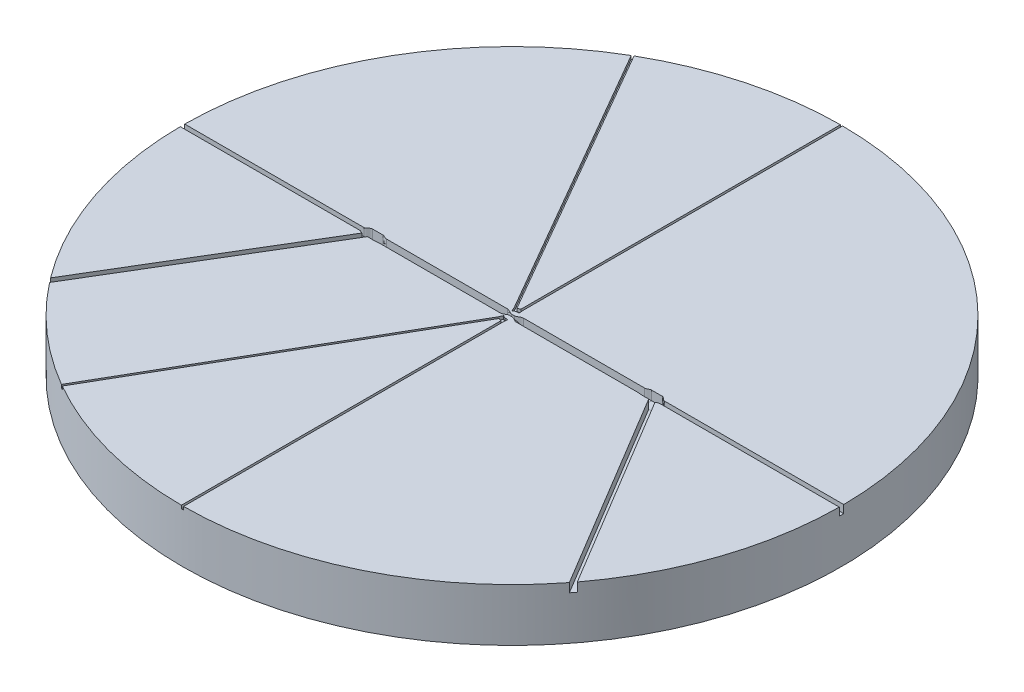
SolidWorks part; units mm, degrees
ref_plane "Front Plane" through (0, 0, 0) normal (0, 0, 1) x (1, 0, 0)
ref_plane "Top Plane" through (0, 0, 0) normal (0, 1, 0) x (1, 0, 0)
ref_plane "Right Plane" through (0, 0, 0) normal (1, 0, 0) x (0, 0, -1)
sketch "Sketch1" plane through (0, 0, 0) normal (0, 1, 0) x (1, 0, 0)
  circle A0 centre (0, 0) radius 12.5
extrude "Boss-Extrude1" add sketch "Sketch1" against normal blind 2
sketch "Sketch2" plane through (0, -2, 0) normal (0, -1, 0) x (-1, 0, 0)
  line L1 (0, 14) -> (14, 14)
  line L2 (0, 14) -> (0, -14)
  line L3 (0, -14) -> (14, -14)
  line L4 (14, 14) -> (14, -14)
extrude "Cut-Extrude1" cut sketch "Sketch2" against normal blind 3
sketch "Sketch4" plane through (0, 0, 0) normal (-1, 0, 0) x (0, 0, 1)
  line L1 (-0.04, 0.121) -> (0.04, 0.121)
  line L2 (-0.04, 0.121) -> (-0.04, -0.121)
  line L3 (-0.04, -0.121) -> (0.04, -0.121)
  line L4 (0.04, 0.121) -> (0.04, -0.121)
  line L5 (-0.04, 0.121) -> (0.04, -0.121) construction
  line L6 (-0.04, -0.121) -> (0.04, 0.121) construction
  point P0 (0, 0)
extrude "Cut-Extrude2" cut sketch "Sketch4" against normal blind 0.05
ref_plane "Plane1" through (0.3, 0, 0) normal (-1, 0, 0) x (0, 0, 1)
sketch "Sketch5" plane through (0.3, 0, 0) normal (-1, 0, 0) x (0, 0, 1)
  line L1 (-0.135, 0.291) -> (0.135, 0.291)
  line L2 (-0.135, 0.291) -> (-0.135, -0.291)
  line L3 (-0.135, -0.291) -> (0.135, -0.291)
  line L4 (0.135, 0.291) -> (0.135, -0.291)
  line L5 (-0.135, 0.291) -> (0.135, -0.291) construction
  line L6 (-0.135, -0.291) -> (0.135, 0.291) construction
  point P1 (0, 0)
extrude "Cut-Extrude3" cut sketch "Sketch5" against normal blind 5
sketch "Sketch7" plane through (0.05, 0, 0) normal (-1, 0, 0) x (0, 0, 1)
  line L1 (-0.04, 0) -> (0.04, 0)
  line L2 (-0.04, 0) -> (-0.04, -0.121)
  line L3 (-0.04, -0.121) -> (0.04, -0.121)
  line L4 (0.04, 0) -> (0.04, -0.121)
sketch "Sketch8" plane through (0.3, 0, 0) normal (-1, 0, 0) x (0, 0, 1)
  line L1 (-0.135, 0) -> (0.135, 0)
  line L2 (-0.135, 0) -> (-0.135, -0.291)
  line L3 (-0.135, -0.291) -> (0.135, -0.291)
  line L4 (0.135, 0) -> (0.135, -0.291)
loft "Cut-Loft3" cut profiles "Sketch7", "Sketch8" start constraint normal to profile start tangent length 1 end constraint normal to profile end tangent length 1 connector at (0.05, 0, 0.04) connector at (0.3, 0, 0.135)
ref_point "Point1"
ref_axis "Axis1" through (0, 0, 0) along (1, 0, 0)
ref_plane "Plane2" through (5.3, 0, 0) normal (-1, 0, 0) x (0, 0, 1)
sketch "Sketch9" plane through (0, 0, 0) normal (0, 1, 0) x (1, 0, 0)
  line L0 (5.3, 0) -> (10.5, -8.6603)
  line L1 (5.3, 0.135) -> (5.3, -0.135) construction
ref_plane "Plane3" through (5.3, 0, 0) normal (0.5148, 0, 0.8573) x (0.8573, 0, -0.5148)
ref_plane "Plane4" through (1.4559, 0, 2.4248) normal (0.5148, 0, 0.8573) x (0.8573, 0, -0.5148)
sketch "Sketch15" plane through (1.4559, 0, 2.4248) normal (0.5148, 0, 0.8573) x (0.8573, 0, -0.5148)
  line L1 (4.4974, -0.3363) -> (4.6976, -0.3363)
  line L2 (4.4974, -0.3363) -> (4.4974, 0)
  line L3 (4.4974, 0) -> (4.6976, 0)
  line L4 (4.6976, -0.3363) -> (4.6976, 0)
  line L5 (4.4974, -0.3363) -> (4.6976, 0) construction
  line L6 (4.4974, 0) -> (4.6976, -0.3363) construction
  point P0 (4.5975, -0.1682)
extrude "Cut-Extrude4" cut sketch "Sketch15" along normal blind 10
sketch "Sketch20" plane through (5.3, 0, 0) normal (-1, 0, 0) x (0, 0, 1)
  line L1 (-0.2, 0) -> (0.15, 0)
  line L2 (-0.2, 0) -> (-0.2, -0.35)
  line L3 (-0.2, -0.35) -> (0.15, -0.35)
  line L4 (0.15, 0) -> (0.15, -0.35)
  line L5 (-0.2, 0) -> (0.15, -0.35) construction
  line L6 (-0.2, -0.35) -> (0.15, 0) construction
  point P0 (-0.025, -0.175)
extrude "Cut-Extrude7" cut sketch "Sketch20" against normal blind 0.2 and the other way blind 0.2
ref_plane "Plane5" through (4.9, 0, 0) normal (-1, 0, 0) x (0, 0, 1)
sketch "Sketch21" plane through (4.9, 0, 0) normal (-1, 0, 0) x (0, 0, 1)
  line L1 (-0.135, 0) -> (0.135, 0)
  line L2 (-0.135, 0) -> (-0.135, -0.291)
  line L3 (-0.135, -0.291) -> (0.135, -0.291)
  line L4 (0.135, 0) -> (0.135, -0.291)
sketch "Sketch22" plane through (5.1, 0, 0) normal (1, 0, 0) x (0, 0, -1)
  line L1 (-0.15, 0) -> (0.2, 0)
  line L2 (-0.15, 0) -> (-0.15, -0.35)
  line L3 (-0.15, -0.35) -> (0.2, -0.35)
  line L4 (0.2, 0) -> (0.2, -0.35)
loft "Cut-Loft4" cut profiles "Sketch22", "Sketch21" start constraint normal to profile start tangent length 1 end constraint normal to profile end tangent length 1 connector at (5.1, 0, 0.15) connector at (4.9, 0, 0.135)
ref_plane "Plane6" through (5.7, 0, 0) normal (-1, 0, 0) x (0, 0, 1)
sketch "Sketch23" plane through (5.7, 0, 0) normal (-1, 0, 0) x (0, 0, 1)
  line L0 (-0.04, 0) -> (-12.5, 0) construction
  line L1 (-0.085, 0) -> (0.085, 0)
  line L2 (-0.085, 0) -> (-0.085, -0.3)
  line L3 (-0.085, -0.3) -> (0.085, -0.3)
  line L4 (0.085, 0) -> (0.085, -0.3)
sketch "Sketch24" plane through (5.5, 0, 0) normal (-1, 0, 0) x (0, 0, 1)
  line L1 (0.15, 0) -> (-0.2, 0)
  line L2 (0.15, 0) -> (0.15, -0.35)
  line L3 (0.15, -0.35) -> (-0.2, -0.35)
  line L4 (-0.2, 0) -> (-0.2, -0.35)
loft "Cut-Loft5" cut profiles "Sketch24", "Sketch23" start constraint normal to profile start tangent length 1 end constraint normal to profile end tangent length 1 connector at (5.5, 0, -0.2) connector at (5.7, 0, -0.085)
extrude "Cut-Extrude8" cut sketch "Sketch23<2>" against normal blind 8
sketch "Sketch23<2>" plane through (5.7, 0, 0) normal (-1, 0, 0) x (0, 0, 1) same geometry as "Sketch23"
mirror "Mirror1" about plane through (0, 0, 0) normal (1, 0, 0) of bodies 113
ref_plane "Plane7" through (0, 0, 0.212) normal (0, 0, -1) x (-1, 0, 0)
sketch "Sketch26" plane through (0, 0, 0.212) normal (0, 0, -1) x (-1, 0, 0)
  line L1 (-0.04, 0) -> (0.04, 0)
  line L2 (-0.04, 0) -> (-0.04, -0.121)
  line L3 (-0.04, -0.121) -> (0.04, -0.121)
  line L4 (0.04, 0) -> (0.04, -0.121)
  line L5 (-0.04, 0) -> (0.04, -0.121) construction
  line L6 (-0.04, -0.121) -> (0.04, 0) construction
  point P0 (0, -0.0605)
extrude "Cut-Extrude9" cut sketch "Sketch26" against normal blind 13
sketch "Sketch27" plane through (0, 0, 0) normal (0, 1, 0) x (1, 0, 0)
  line L0 (0, 0) -> (-1.6943, -2.9346)
  line L1 (0.0551, -0.212) -> (-0.0551, -0.212) construction
  line L2 (0.0625, -0.3002) -> (-0.0625, -0.3002)
  line L3 (0.0625, -0.3002) -> (0.0625, -0.212)
  line L4 (0.0625, -0.212) -> (-0.0625, -0.212)
  line L5 (-0.0625, -0.3002) -> (-0.0625, -0.212)
  line L6 (0.0625, -0.3002) -> (-0.0625, -0.212) construction
  line L7 (0.0625, -0.212) -> (-0.0625, -0.3002) construction
  point P3 (0, -0.2561)
ref_plane "Plane8" through (0, 0, 0) normal (-0.5, 0, 0.866) x (0.866, 0, 0.5)
ref_point "Point2"
ref_plane "Plane9" through (-0.1074, 0, 0.1861) normal (-0.5, 0, 0.866) x (0.866, 0, 0.5)
sketch "Sketch28" plane through (-0.1074, 0, 0.1861) normal (-0.5, 0, 0.866) x (0.866, 0, 0.5)
  line L1 (-0.04, 0) -> (0.04, 0)
  line L2 (-0.04, 0) -> (-0.04, -0.121)
  line L3 (-0.04, -0.121) -> (0.04, -0.121)
  line L4 (0.04, 0) -> (0.04, -0.121)
  line L5 (-0.04, 0) -> (0.04, -0.121) construction
  line L6 (-0.04, -0.121) -> (0.04, 0) construction
  point P0 (0, -0.0605)
extrude "Cut-Extrude10" cut sketch "Sketch28" along normal blind 13
mirror "Mirror2" about plane through (0, 0, 0) normal (0, 0, 1) of "Cut-Extrude9", "Cut-Extrude10"
sketch "Sketch29" plane through (0, -0.121, 0) normal (0, 1, 0) x (1, 0, 0)
  line L0 (-0.0625, -0.212) -> (-0.1584, -0.1566)
  line L1 (-1.7215, 0.7458) -> (1.5066, -1.1179) construction
  line L2 (-0.1584, -0.1566) -> (-0.2204, -0.3017)
  line L3 (-6.2846, -10.8053) -> (-0.1421, -0.1661) construction
  line L4 (-0.2204, -0.3017) -> (-0.1511, -0.3417)
  line L5 (-6.2153, -10.8453) -> (-0.0728, -0.2061) construction
  line L6 (-0.1511, -0.3417) -> (-0.04, -0.3752)
  line L7 (-0.04, -12.4999) -> (-0.04, -0.212) construction
  line L8 (-0.04, -0.3752) -> (0.04, -0.3752)
  line L9 (0.04, -12.4999) -> (0.04, -0.212) construction
  line L10 (0.04, -0.3752) -> (0.0554, -0.212)
  line L11 (0.0625, -0.212) -> (-0.0625, -0.212) construction
  line L12 (0.0554, -0.212) -> (-0.0625, -0.212)
extrude "Cut-Extrude11" cut sketch "Sketch29" along normal blind 0.121
mirror "Mirror3" about plane through (0, 0, 0) normal (0, 0, 1) of "Cut-Extrude11"
